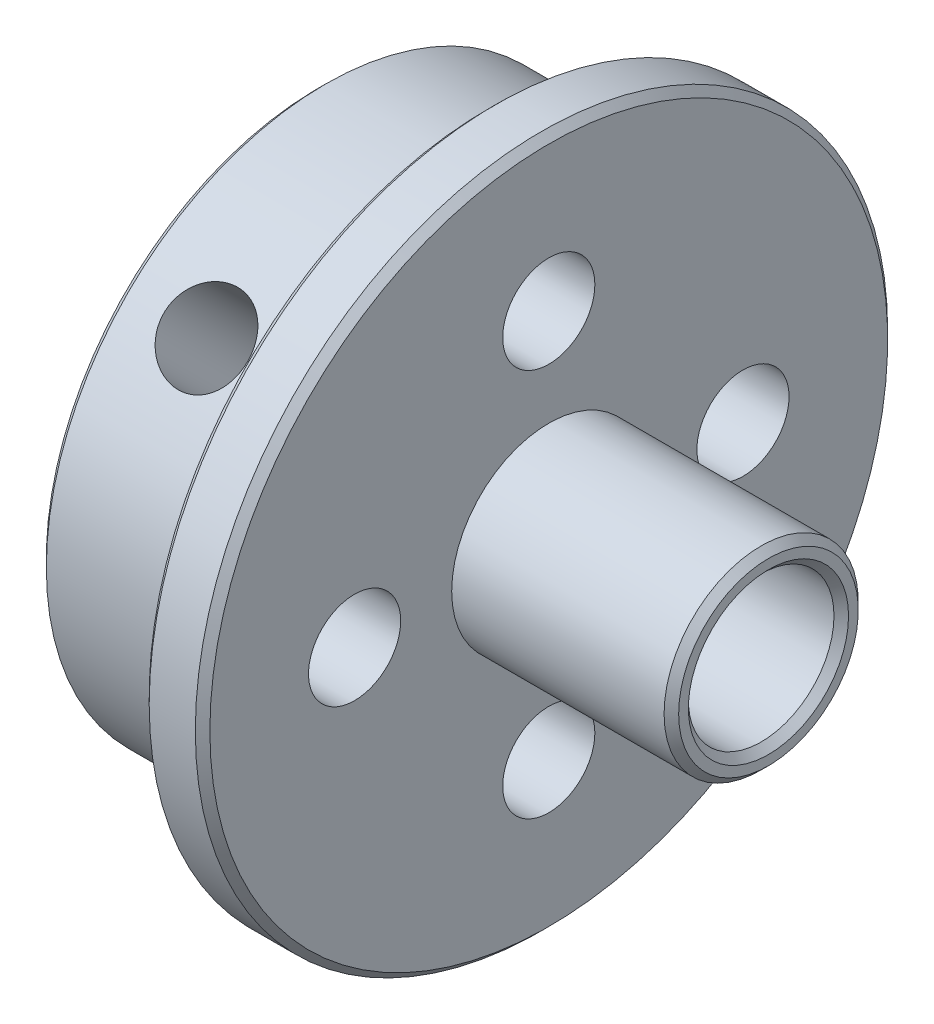
SolidWorks part; units mm, degrees
material "6061-T6 (SS)"
ref_plane "Front" through (0, 0, 0) normal (0, 0, 1) x (1, 0, 0)
ref_plane "Top" through (0, 0, 0) normal (0, 1, 0) x (1, 0, 0)
ref_plane "Right" through (0, 0, 0) normal (1, 0, 0) x (0, 0, -1)
ref_axis "side-side" through (80.9, 0, 0) along (-1, 0, 0)
ref_axis "up-down" through (0, 50, 0) along (0, -1, 0)
ref_axis "front-back" through (0, 0, -80.9) along (0, 0, 1)
sketch "Sketch1" plane through (0, 0, 0) normal (0, 0, 1) x (1, 0, 0)
  line L0 (0, 0) -> (14.0331, 0) construction
  line L1 (-9.5, 3) -> (2.5, 3)
  line L2 (-9.5, 3) -> (-9.5, 11.5)
  line L3 (-2.5, 14.2621) -> (0, 14.2621)
  line L4 (2.5, 3) -> (2.5, 4)
  line L5 (0, -50) -> (0, 50) construction
  line L7 (2.5, 4) -> (0, 4)
  line L8 (0, 14.2621) -> (0, 4)
  line L11 (-9.5, 11.5) -> (-2.5, 11.5)
  line L12 (-2.5, 14.2621) -> (-2.5, 11.5)
  dimension "D1" = 6
  dimension "D2" = 8
  dimension "D3" = 2.5
  dimension "D4" = 2.5
  dimension "D5" = 23
  dimension "D6" = 28.5242
  dimension "D7" = 12
  dimension "D8" = 7
revolve "Revolve1" add sketch "Sketch1" angle 360 about L0
hole_wizard "#6 Clearance Hole1" positions "Sketch2" profile "Sketch3" hole size "#6" standard "ANSI Inch" end condition through all
sketch "Sketch2" plane through (0, 0, 0) normal (1, 0, 0) x (0, 0, -1)
  circle A0 centre (0, 0) radius 8 construction
  point P4 (0, 8)
  point P6 (0, -8)
  point P8 (8, 0)
  point P10 (-8, 0)
  dimension "D1" = 16
sketch "Sketch3" plane through (0, 0, 8) normal (0, 1, 0) x (0, 0, -1)
  line L0 (0, 0) -> (0, 9.5)
  line L1 (0, 9.5) -> (1.8986, 9.5)
  line L2 (1.8986, 9.5) -> (1.8986, 0)
  line L5 (1.8986, 0) -> (0, 0)
  line L11 (0, -6.35) -> (0, 107.95) construction
  dimension "Thru Hole Dia." = 3.7973
  dimension "Thru Hole Depth" = 9.5
ref_plane "Plane1" through (0, 0, 0) normal (0, 0.7071, 0.7071) x (-1, 0, 0)
sketch "Sketch4" plane through (0, 0, 0) normal (0, 0.7071, 0.7071) x (-1, 0, 0)
  line L0 (9.5, -11.5) -> (9.5, 11.5) construction
  circle A0 centre (6, 0) radius 1.25
  dimension "D2" = 2.5
  dimension "D1" = 3.5
extrude "Boss-Extrude1" add sketch "Sketch4" along normal blind 1.5 from offset 10
hole_wizard "#8-32 Tapped Hole1" positions "Sketch5" profile "Sketch6" tap size "#8-32" standard "ANSI Inch"
sketch "Sketch5" plane through (0, 8.1317, 8.1317) normal (0, 0.7071, 0.7071) x (1, 0, 0)
  point P0 (-6, 0)
sketch "Sketch6" plane through (-6, 8.1317, 8.1317) normal (1, 0, 0) x (0, -0.7071, 0.7071)
  line L0 (0, 0) -> (0, 11.7458)
  line L1 (0, 11.7458) -> (1.7272, 10.708)
  line L2 (1.7272, 10.708) -> (1.7272, 0)
  line L5 (1.7272, 0) -> (0, 0)
  line L10 (0, 11.7458) -> (-1.7272, 10.708) construction
  line L11 (0, -6.35) -> (0, 107.95) construction
  dimension "Tap Drill Dia." = 3.4544
  dimension "Tap Drill Depth" = 10.708
  dimension "Drill Angle" = 118
other "Move Face1" face at (2.5, 0, 4) offset 6.55 parameters "D1"=6.55
chamfer "Chamfer1" distance 0.3 angle 45 6 edges at (-9.5, 0, 11.5) (-2.5, 0, 14.2621) (0, 0, 14.2621) (9.05, 0, 3) (9.05, 0, 4) (-9.5, 0, 3)
